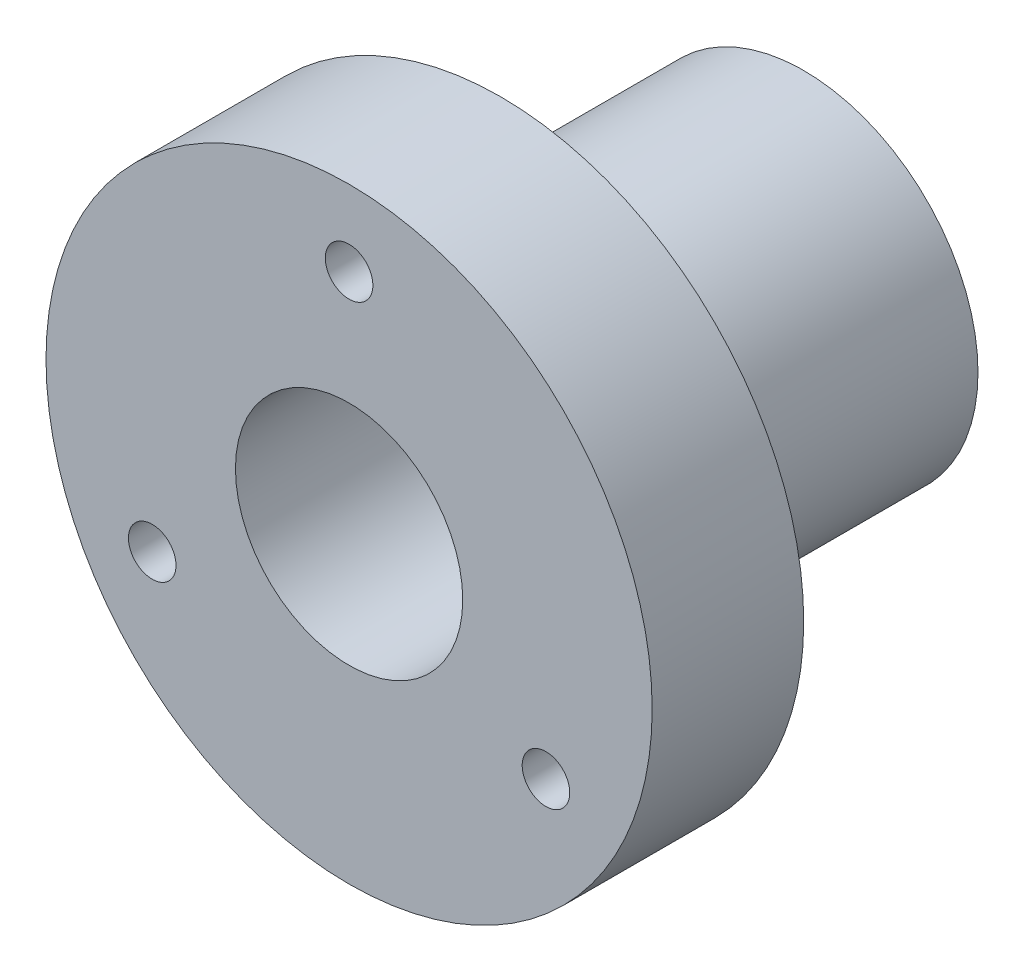
SolidWorks part; units mm, degrees
material "1060 Alloy"
ref_plane "Front" through (0, 0, 0) normal (0, 0, 1) x (1, 0, 0)
ref_plane "Top" through (0, 0, 0) normal (0, 1, 0) x (1, 0, 0)
ref_plane "Right" through (0, 0, 0) normal (1, 0, 0) x (0, 0, -1)
sketch "Sketch1" plane through (0, 0, 0) normal (0, 0, 1) x (1, 0, 0)
  circle A0 centre (0, 0) radius 25.4
  dimension "D1" = 50.8
extrude "Boss-Extrude1" add sketch "Sketch1" against normal blind 12.7
sketch "Sketch9" plane through (0, 0, 0) normal (0, 0, 1) x (1, 0, 0)
  circle A0 centre (0, 0) radius 14.605
  dimension "D1" = 29.21
extrude "Boss-Extrude2" add sketch "Sketch9" against normal blind 38.1
sketch "Sketch10" plane through (0, 0, -12.7) normal (0, 0, -1) x (-1, 0, 0)
  circle A0 centre (0, 0) radius 19.05 construction
  dimension "D1" = 38.1
hole_wizard "#10-24 Tapped Hole1" positions "Sketch11" profile "Sketch12" tap size "#10-24" standard "ANSI Inch" end condition through all
sketch "Sketch11" plane through (0, 0, -12.7) normal (0, 0, -1) x (-1, 0, 0)
  circle A0 centre (0, 0) radius 19.05 construction
  point P0 (0, 19.05)
  point P4 (-16.4978, -9.525)
  point P6 (16.4978, -9.525)
  dimension "D1" = 120
  dimension "D2" = 120
cosmetic thread "Hole Thread4" parameters "D2"=4.826
cosmetic thread "Hole Thread5" parameters "D2"=4.826
cosmetic thread "Hole Thread6" parameters "D2"=4.826
sketch "Sketch12" plane through (0, 19.05, -12.7) normal (1, 0, 0) x (0, 1, 0)
  line L0 (0, 0) -> (0, 12.7)
  line L1 (0, 12.7) -> (1.9939, 12.7)
  line L2 (1.9939, 12.7) -> (1.9939, 0)
  line L5 (1.9939, 0) -> (0, 0)
  line L11 (0, -6.35) -> (0, 107.95) construction
  dimension "Thru Tap Drill Dia." = 3.9878
  dimension "Thru Tap Drill Depth" = 12.7
hole_wizard "Ø8.4 (8.4) Diameter Hole2" positions "Sketch13" profile "Sketch14" hole size "Ø8.4" standard "ANSI Metric" end condition through all
sketch "Sketch13" plane through (0, 0, -38.1) normal (0, 0, -1) x (-1, 0, 0)
  point P0 (0, 0)
sketch "Sketch14" plane through (0, 0, -38.1) normal (1, 0, 0) x (0, 1, 0)
  line L0 (0, 0) -> (0, 38.1)
  line L1 (0, 38.1) -> (4.2, 38.1)
  line L2 (4.2, 38.1) -> (4.2, 0)
  line L5 (4.2, 0) -> (0, 0)
  line L11 (0, -6.35) -> (0, 107.95) construction
  dimension "Thru Hole Dia." = 8.4
  dimension "Thru Hole Depth" = 38.1
hole_wizard "Ø10.0 (10) Diameter Hole1" positions "Sketch15" profile "Sketch16" hole size "Ø10.0" standard "ANSI Metric"
sketch "Sketch15" plane through (0, 0, -38.1) normal (0, 0, -1) x (-1, 0, 0)
  point P0 (0, 0)
sketch "Sketch16" plane through (0, 0, -38.1) normal (1, 0, 0) x (0, 1, 0)
  line L0 (0, 0) -> (0, 13.1643)
  line L1 (0, 13.1643) -> (5, 10.16)
  line L2 (5, 10.16) -> (5, 0)
  line L5 (5, 0) -> (0, 0)
  line L10 (0, 13.1643) -> (-5, 10.16) construction
  line L11 (0, -6.35) -> (0, 107.95) construction
  dimension "Hole Dia." = 10
  dimension "Hole Depth" = 10.16
  dimension "Drill Angle" = 118
hole_wizard "3/4 (0.75) Diameter Hole1" positions "Sketch17" profile "Sketch18" hole size "3/4" standard "ANSI Inch"
sketch "Sketch17" plane through (0, 0, 0) normal (0, 0, 1) x (1, 0, 0)
  point P0 (0, 0)
sketch "Sketch18" plane through (0, 0, 0) normal (1, 0, 0) x (0, -1, 0)
  line L0 (0, 0) -> (0, 28.5832)
  line L1 (0, 28.5832) -> (9.525, 22.86)
  line L2 (9.525, 22.86) -> (9.525, 0)
  line L5 (9.525, 0) -> (0, 0)
  line L10 (0, 28.5832) -> (-9.525, 22.86) construction
  line L11 (0, -6.35) -> (0, 107.95) construction
  dimension "Hole Dia." = 19.05
  dimension "Hole Depth" = 22.86
  dimension "Drill Angle" = 118
